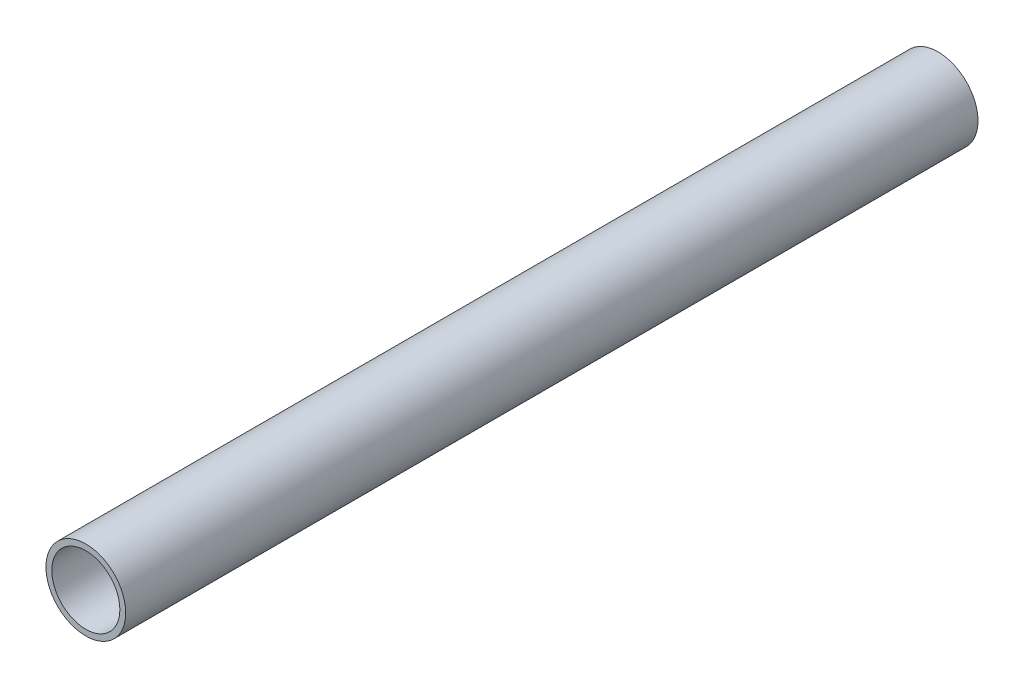
SolidWorks part; units mm, degrees
material "1060 Alloy"
ref_plane "Front" through (0, 0, 0) normal (0, 0, 1) x (1, 0, 0)
ref_plane "Top" through (0, 0, 0) normal (0, 1, 0) x (1, 0, 0)
ref_plane "Right" through (0, 0, 0) normal (1, 0, 0) x (0, 0, -1)
sketch "Sketch1" plane through (0, 0, 0) normal (0, 0, 1) x (1, 0, 0)
  circle A0 centre (0, 0) radius 9.36
  circle A1 centre (0, 0) radius 7.99
extrude "Extrude1" add sketch "Sketch1" along normal blind 200
